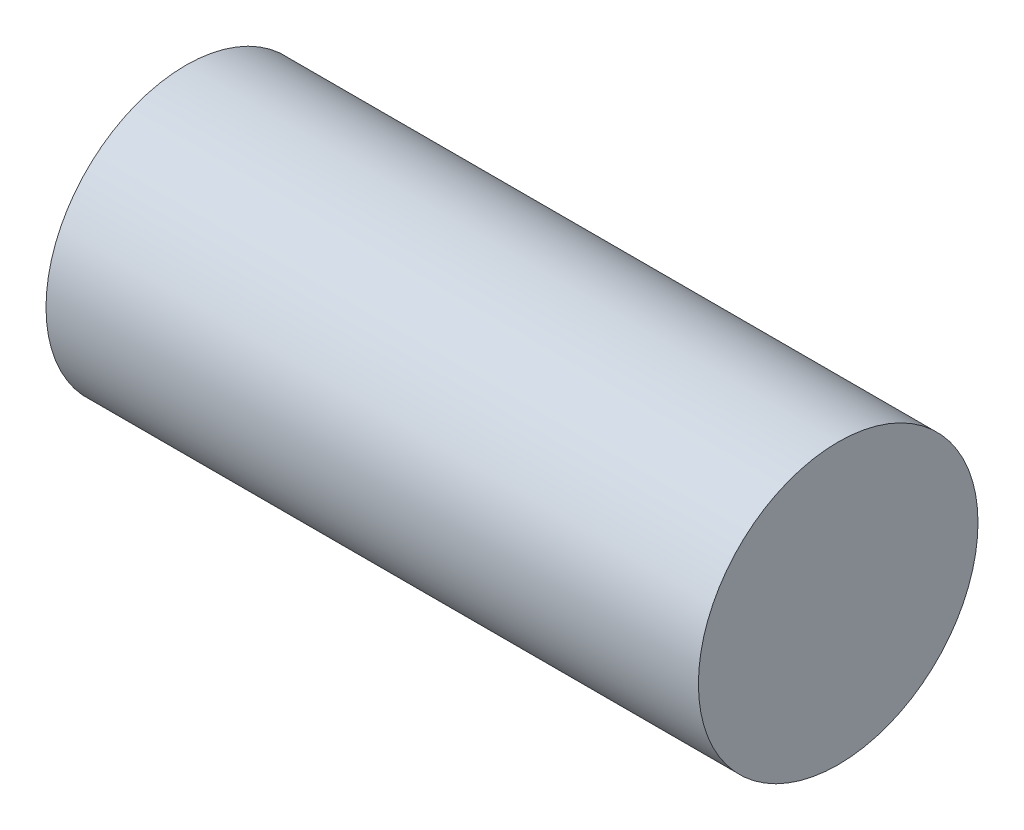
SolidWorks part; units mm, degrees
material "AISI 4340 Steel, normalized"
ref_plane "Front Plane" through (0, 0, 0) normal (0, 0, 1) x (1, 0, 0)
ref_plane "Top Plane" through (0, 0, 0) normal (0, 1, 0) x (1, 0, 0)
ref_plane "Right Plane" through (0, 0, 0) normal (1, 0, 0) x (0, 0, -1)
sketch "Sketch1" plane through (0, 0, 0) normal (1, 0, 0) x (0, 0, -1)
  circle A0 centre (0, 0) radius 38.1
  dimension "D1" = 76.2
extrude "Boss-Extrude1" add sketch "Sketch1" along normal blind 177.8
